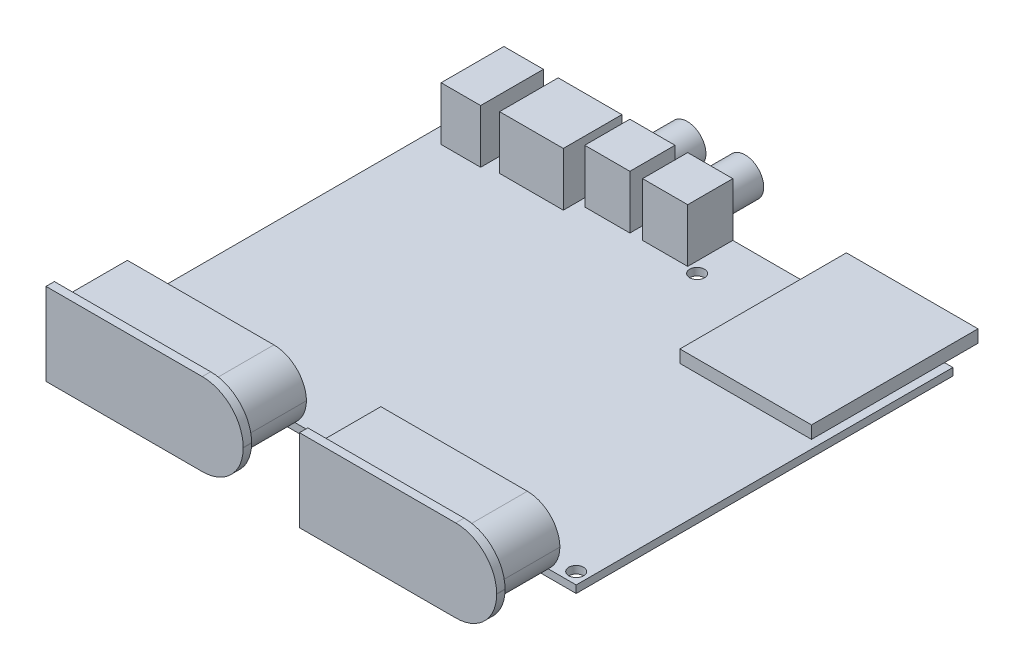
SolidWorks part; units mm, degrees
ref_plane "Front Plane" through (0, 0, 0) normal (0, 0, 1) x (1, 0, 0)
ref_plane "Top Plane" through (0, 0, 0) normal (0, 1, 0) x (1, 0, 0)
ref_plane "Right Plane" through (0, 0, 0) normal (1, 0, 0) x (0, 0, -1)
sketch "Sketch1" plane through (0, 0, 0) normal (0, 1, 0) x (1, 0, 0)
  line L1 (0, 0) -> (100, 0)
  line L2 (0, 0) -> (0, 81)
  line L3 (0, 81) -> (100, 81)
  line L4 (100, 0) -> (100, 81)
  dimension "D1" = 81
  dimension "D2" = 100
extrude "Boss-Extrude1" add sketch "Sketch1" along normal blind 1.6
sketch "Sketch2" plane through (0, 0, 0) normal (0, 0, 1) x (1, 0, 0)
  line L0 (0, 0) -> (100, 0) construction
  line L1 (96.5, 0) -> (58, 0)
  line L2 (96.5, 0) -> (96.5, 13.8)
  line L3 (96.5, 13.8) -> (58, 13.8)
  line L4 (58, 0) -> (58, 13.8)
  line L5 (100, 1.6) -> (100, 0) construction
  line L6 (3.5, 0) -> (42, 0)
  line L7 (3.5, 0) -> (3.5, 13.8)
  line L8 (3.5, 13.8) -> (42, 13.8)
  line L9 (42, 0) -> (42, 13.8)
  line L10 (0, 1.6) -> (0, 0) construction
  dimension "D1" = 38.5
  dimension "D2" = 13.8
  dimension "D3" = 3.5
  dimension "D4" = 3.5
  dimension "D5" = 16
extrude "Boss-Extrude2" add sketch "Sketch2" along normal blind 14
sketch "Sketch3" plane through (0, 0, 14) normal (0, 0, 1) x (1, 0, 0)
  line L0 (42, 13.8) -> (3.5, 13.8) construction
  line L1 (1.8, -1.7) -> (44.2, -1.7)
  line L2 (1.8, -1.7) -> (1.8, 16)
  line L3 (1.8, 16) -> (44.2, 16)
  line L4 (44.2, -1.7) -> (44.2, 16)
  line L5 (3.5, 0) -> (42, 0) construction
  line L6 (3.5, 13.8) -> (3.5, 0) construction
  line L7 (42, 0) -> (42, 13.8) construction
  line L8 (96.5, 13.8) -> (58, 13.8) construction
  line L9 (56.3, -1.7) -> (98.7, -1.7)
  line L10 (56.3, -1.7) -> (56.3, 16)
  line L11 (56.3, 16) -> (98.7, 16)
  line L12 (98.7, -1.7) -> (98.7, 16)
  line L13 (96.5, 0) -> (96.5, 13.8) construction
  line L14 (58, 0) -> (96.5, 0) construction
  line L15 (58, 13.8) -> (58, 0) construction
  dimension "D1" = 2.2
  dimension "D2" = 1.7
  dimension "D3" = 1.7
  dimension "D4" = 2.2
  dimension "D5" = 2.2
  dimension "D6" = 2.2
  dimension "D7" = 1.7
  dimension "D8" = 1.7
extrude "Boss-Extrude3" add sketch "Sketch3" along normal blind 1.8
sketch "Sketch4" plane through (0, 1.6, 0) normal (0, 1, 0) x (1, 0, 0)
  line L0 (100, 81) -> (0, 81) construction
  line L1 (3.4565, 81) -> (11.9565, 81)
  line L2 (3.4565, 81) -> (3.4565, 67.5)
  line L3 (3.4565, 67.5) -> (11.9565, 67.5)
  line L4 (11.9565, 81) -> (11.9565, 67.5)
  line L6 (15.131, 81) -> (28.831, 81)
  line L7 (15.131, 81) -> (15.131, 68.4)
  line L8 (15.131, 68.4) -> (28.831, 68.4)
  line L9 (28.831, 81) -> (28.831, 68.4)
  line L10 (30.5456, 81) -> (40.2456, 81)
  line L11 (30.5456, 81) -> (30.5456, 71.3)
  line L12 (30.5456, 71.3) -> (40.2456, 71.3)
  line L13 (40.2456, 81) -> (40.2456, 71.3)
  line L14 (42.9772, 81) -> (52.6772, 81)
  line L15 (42.9772, 81) -> (42.9772, 71.3)
  line L16 (42.9772, 71.3) -> (52.6772, 71.3)
  line L17 (52.6772, 81) -> (52.6772, 71.3)
  dimension "D4" = 8.5
  dimension "D5" = 13.7
  dimension "D6" = 9.7
  dimension "D7" = 9.7
  dimension "D8" = 13.5
  dimension "D9" = 12.6
  dimension "D10" = 9.7
  dimension "D11" = 9.7
extrude "Boss-Extrude4" add sketch "Sketch4" along normal blind 11.5
sketch "Sketch5" plane through (0, 1.6, 0) normal (0, 1, 0) x (1, 0, 0)
  line L1 (98.2, 88.2) -> (69.9, 88.2)
  line L2 (98.2, 88.2) -> (98.2, 52.4)
  line L3 (98.2, 52.4) -> (69.9, 52.4)
  line L4 (69.9, 88.2) -> (69.9, 52.4)
  line L5 (100, 81) -> (52.6772, 81) construction
  line L6 (100, 0) -> (100, 81) construction
  dimension "D1" = 35.8
  dimension "D2" = 28.3
  dimension "D3" = 28.6
  dimension "D4" = 1.8
extrude "Boss-Extrude5" add sketch "Sketch5" along normal blind 2.7
sketch "Sketch6" plane through (0, 0, -81) normal (0, 0, -1) x (-1, 0, 0)
  circle A0 centre (-47.8272, 7.35) radius 4
  circle A1 centre (-35.3956, 7.35) radius 4
  dimension "D1" = 8
  dimension "D2" = 8
extrude "Boss-Extrude6" add sketch "Sketch6" along normal blind 7.5
hole_wizard "M3 Clearance Slot1" positions "Sketch7" profile "Sketch8" size "M3" standard "ANSI Metric" slot yes end condition through all
sketch "Sketch7" plane through (0, 1.6, 0) normal (0, 1, 0) x (1, 0, 0)
  line L0 (0, 81) -> (0, 0) construction
  line L1 (0, 0) -> (3.5, 0) construction
  line L2 (100, 0) -> (100, 81) construction
  line L3 (96.5, 0) -> (100, 0) construction
  line L4 (69.9, 81) -> (52.6772, 81) construction
  point P0 (55, 71)
  point P2 (97.5, 2.5)
  point P4 (2.5, 2.5)
  dimension "D1" = 2.5
  dimension "D2" = 2.5
  dimension "D3" = 2.5
  dimension "D4" = 2.5
  dimension "D5" = 10
  dimension "D6" = 45
sketch "Sketch8" plane through (55, 1.6, -71) normal (1, 0, 0) x (0, 0, 1)
  line L0 (0, 0) -> (0, 3.3)
  line L1 (0, 3.3) -> (1.6, 3.3)
  line L2 (1.6, 3.3) -> (1.6, 0)
  line L5 (1.6, 0) -> (0, 0)
  line L11 (0, -6.35) -> (0, 107.95) construction
  dimension "Thru Hole Dia." = 3.2
  dimension "Thru Hole Depth" = 3.3
fillet "Fillet1" radius 7 4 edges at (42, 0, 7) (42, 13.8, 7) (96.5, 0, 7) (96.5, 13.8, 7)
fillet "Fillet2" radius 8.8 4 edges at (98.7, -1.7, 14.9) (44.2, -1.7, 14.9) (44.2, 16, 14.9) (98.7, 16, 14.9)
